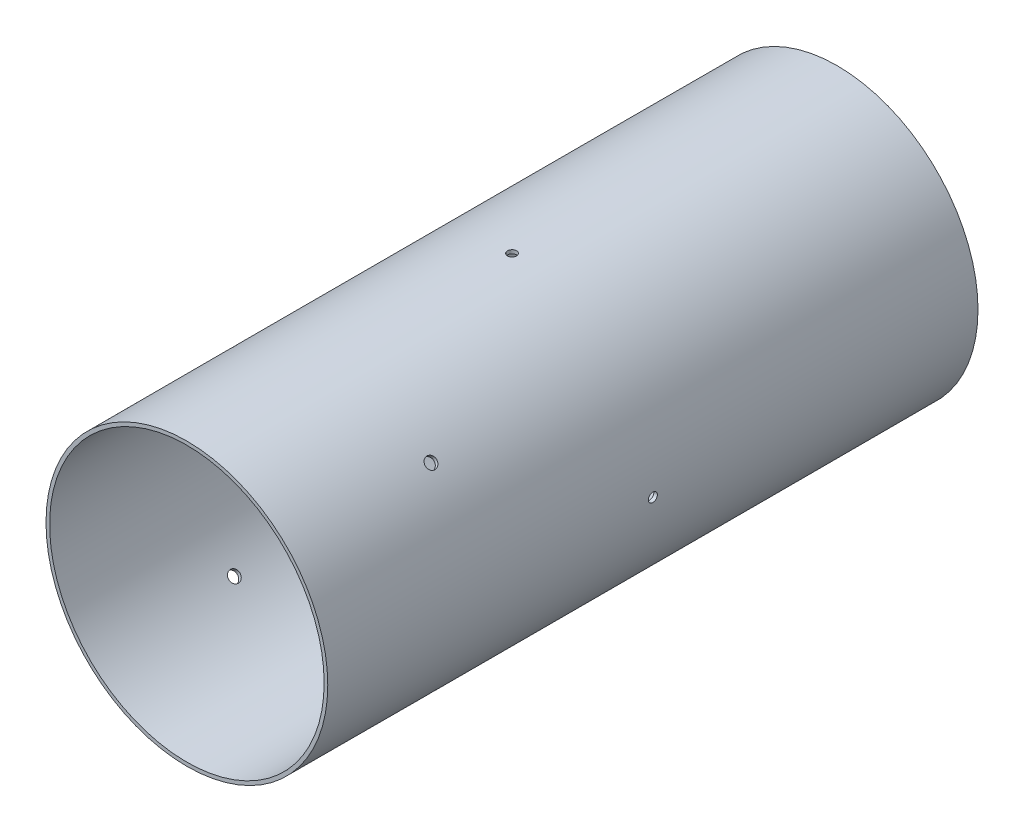
SolidWorks part; units mm, degrees
ref_plane "Front Plane" through (0, 0, 0) normal (0, 0, 1) x (1, 0, 0)
ref_plane "Top Plane" through (0, 0, 0) normal (0, 1, 0) x (1, 0, 0)
ref_plane "Right Plane" through (0, 0, 0) normal (1, 0, 0) x (0, 0, -1)
sketch "Sketch1" plane through (0, 0, 0) normal (0, 0, 1) x (1, 0, 0)
  circle A0 centre (0, 0) radius 49.53
  circle A1 centre (0, 0) radius 48.26
  dimension "D1" = 99.06
  dimension "D2" = 96.52
extrude "Boss-Extrude1" add sketch "Sketch1" along normal blind 228.6
extrude "Cut-Extrude1" cut sketch "Sketch2" against normal blind 12.7
sketch "Sketch2" plane through (-120.5803, -48.7382, -78.9954) normal (-0.7071, 0.7071, 0) x (0.7071, 0.7071, 0)
  circle A0 centre (119.7263, -256.7954) radius 1.9844
pattern_circular "CirPattern1" count 4 over 360 of "Cut-Extrude1"
extrude "Cut-Extrude2" cut sketch "Sketch3" against normal blind 25.4
sketch "Sketch3" plane through (-108.0218, -85.4992, -79.3332) normal (-0.866, 0.5, 0) x (0, 0, 1)
  circle A0 centre (196.8082, 128.0554) radius 2.3813
  circle A1 centre (190.4582, 128.0554) radius 2.3813
extrude "Cut-Extrude3" cut sketch "Sketch4" against normal blind 37.338
sketch "Sketch4" plane through (-33.6632, -130.5648, -80.7782) normal (1, 0, 0) x (0, 0, -1)
  circle A0 centre (-195.0782, 130.5648) radius 1.5875
  point P3 (-80.7782, 130.5648)
  point P4 (-195.0782, 181.3648)
pattern_circular "CirPattern2" count 4 over 360 about axis through (0, 0, 228.6) along (0, 0, -1) of "Cut-Extrude3" reverse direction yes
extrude "Cut-Extrude4" cut sketch "Sketch5" against normal blind 25.4
sketch "Sketch5" plane through (-120.5803, -48.7382, -78.9954) normal (-0.7071, 0.7071, 0) x (0.7071, 0.7071, 0)
  line L0 (68.6723, -129.7954) -> (170.7803, -129.7954) construction
  circle A0 centre (119.7263, -129.7954) radius 1.0922
pattern_circular "CirPattern3" count 2 over 360 of "Cut-Extrude4"
